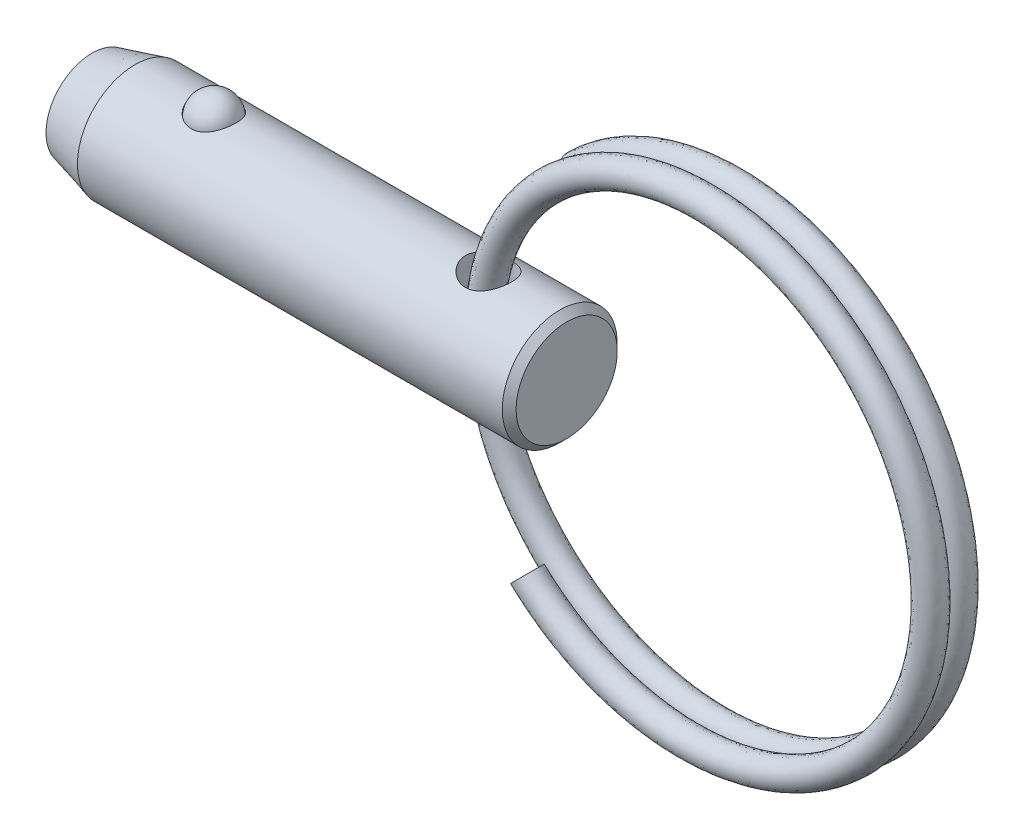
SolidWorks part; units mm, degrees
material "Plain Carbon Steel"
ref_plane "Front" through (0, 0, 0) normal (0, 0, 1) x (1, 0, 0)
ref_plane "Top" through (0, 0, 0) normal (0, 1, 0) x (1, 0, 0)
ref_plane "Right" through (0, 0, 0) normal (1, 0, 0) x (0, 0, -1)
sketch "Sketch1" plane through (0, 0, 0) normal (0, 0, 1) x (1, 0, 0)
  line L0 (13.1064, 2.794) -> (12.7254, 3.175)
  line L1 (12.7254, 3.175) -> (13.1064, 3.175) construction
  line L4 (13.1064, 2.794) -> (13.1064, 0)
  line L5 (13.1064, 3.175) -> (13.1064, 2.794) construction
  line L16 (12.7254, 3.175) -> (-10.7365, 3.175)
  line L17 (-13.1064, 3.175) -> (-13.1064, 2.54) construction
  line L19 (-10.7365, 3.175) -> (-13.1064, 3.175) construction
  line L22 (-13.1064, -3.175) -> (-10.7365, -3.175) construction
  line L23 (-6.3719, 2.8575) -> (-6.3719, -2.8575) construction
  line L24 (-13.1064, 0) -> (13.1064, 0)
  line L27 (13.1064, 0) -> (15.9004, 0) construction
  line L29 (-13.1064, 0) -> (-13.1064, -2.54) construction
  line L36 (7.5184, 0) -> (7.5184, 3.175) construction
  line L37 (-13.1064, 2.54) -> (-13.1064, 0)
  line L38 (-10.7365, -3.175) -> (13.1064, -3.175) construction
  line L39 (-13.1064, -2.54) -> (-13.1064, -3.175) construction
  line L40 (-10.7365, 3.175) -> (-13.1064, 2.54)
  line L42 (-10.7365, -3.175) -> (-13.1064, -2.54) construction
  line L43 (-10.7365, 3.175) -> (-10.7365, -3.175) construction
  circle A2 centre (-6.3719, 2.8575) radius 1.2319 construction
  point P35 (-5.1816, 3.175)
  dimension "A1" = 15
revolve "Revolve1" add sketch "Sketch1" angle 360 about L27
sketch "Sketch2" plane through (0, 0, 0) normal (0, 0, 1) x (1, 0, 0)
  line L0 (-5.1146, 2.8575) -> (-7.6292, 2.8575)
  line L1 (-6.3719, 4.0894) -> (-6.3719, 4.1148) construction
  line L2 (-5.1146, 2.8575) -> (-2.6, 2.8575) construction
  circle A0 centre (-6.3719, 2.8575) radius 1.2319 construction
  circle A1 centre (-6.3719, 2.8575) radius 1.2319 construction
  arc A2 (-7.6292, 2.8575) -> (-5.1146, 2.8575) centre (-6.3719, 2.8575) cw
  dimension "D1" = 0.0254
revolve "Cut-Revolve1" cut sketch "Sketch2" angle 360 about L2
sketch "Sketch3" plane through (0, 0, 0) normal (0, 0, 1) x (1, 0, 0)
  line L0 (-5.14, 2.8575) -> (-7.6038, 2.8575)
  line L1 (-5.14, 2.8575) -> (-2.6762, 2.8575) construction
  circle A0 centre (-6.3719, 2.8575) radius 1.2319 construction
  arc A1 (-5.14, 2.8575) -> (-7.6038, 2.8575) centre (-6.3719, 2.8575) ccw
revolve "Revolve2" add sketch "Sketch3" angle 360 about L1
sketch "Sketch4" plane through (0, 0, 0) normal (0, 0, 1) x (1, 0, 0)
  line L1 (8.7884, -3.175) -> (10.0584, -3.175)
  line L2 (8.7884, -3.175) -> (8.7884, 3.175)
  line L3 (8.7884, 3.175) -> (10.0584, 3.175)
  line L4 (10.0584, -3.175) -> (10.0584, 3.175)
  line L5 (8.7884, -3.175) -> (8.7884, -4.445) construction
  line L6 (10.0584, 3.175) -> (13.1064, 3.175) construction
  line L8 (7.5184, -3.175) -> (7.5184, 3.175) construction
  line L9 (7.5184, 0) -> (8.7884, 0) construction
  line L11 (8.7884, 0) -> (10.0584, 0) construction
  line L12 (12.7254, 3.175) -> (-10.7365, 3.175) construction
  line L14 (-10.7365, -3.175) -> (13.1064, -3.175) construction
  dimension "D1" = 2.54
revolve "Cut-Revolve2" cut sketch "Sketch4" angle 360 about L2
sketch "Sketch5" plane through (0, 0, 0) normal (0, 0, 1) x (1, 0, 0)
  line L0 (0, 0) -> (7.8114, 0) construction
  line L1 (7.8114, 0) -> (7.8114, 3.175) construction
  line L2 (12.7254, 3.175) -> (-10.7365, 3.175) construction
  line L3 (21.2734, 0) -> (34.7354, 0) construction
  line L4 (10.0584, 3.175) -> (9.7654, 3.175) construction
  line L5 (8.7884, 3.175) -> (10.0584, 3.175) construction
  line L6 (8.1912, 3.175) -> (8.1912, -3.175) construction
  line L7 (7.8114, 3.175) -> (7.5184, 3.175) construction
  line L8 (8.7884, -3.175) -> (10.0584, -3.175) construction
  line L9 (8.1912, -3.175) -> (10.0584, -3.175) construction
  line L10 (7.8114, 0) -> (21.2734, 0) construction
  line L12 (9.7654, 3.175) -> (8.1912, 3.175) construction
  line L13 (21.2734, 11.938) -> (21.2734, 13.462) construction
  circle A0 centre (21.2734, 0) radius 13.462
  circle A1 centre (21.2734, 0) radius 11.938 construction
  circle A2 centre (21.2734, 0) radius 12.7 construction
  point P26 (21.2734, 12.7)
curve "Helix/Spiral1" pitch 1.5494 height 1.3557 radius 13.462 left hand yes centre (21.2734, 0, 0) axis (0, 0, -1) start towards (1, 0, 0)
sketch "Sketch6" plane through (114.0038, 0, 0) normal (0, 1, 0) x (0, 0, -1)
  line L0 (0, 104.6684) -> (0, 105.4304) construction
  line L1 (0, 105.4304) -> (0, 106.1924) construction
  circle A0 centre (0, 105.4304) radius 0.762
  dimension "D1" = 1.524
sketch "Sketch7" plane through (0, 0, 0) normal (0, 0, 1) x (1, 0, 0)
  circle A0 centre (21.2734, 0) radius 13.462 construction
  circle A1 centre (21.2734, 0) radius 13.462
curve "Helix/Spiral2" pitch 1.5494 height 1.3557 radius 13.462 left hand yes centre (21.2734, 0, 0) axis (0, 0, 1) start towards (1, 0, 0)
sweep "Sweep1" add profiles "Sketch6" path "Helix/Spiral1"
sweep "Sweep2" add profiles "Sketch6<2>" path "Helix/Spiral2"
sketch "Sketch6<2>" plane through (114.0038, 0, 0) normal (0, 1, 0) x (0, 0, -1) same geometry as "Sketch6"
equation "\"D12@Sketch1\"=\"A@Sketch1\" * 0.80"
equation "\"D2@Sketch1\"=\"A@Sketch1\" * 0.9"
equation "\"D1@Sketch4\" = \"A@Sketch1\" / 2.5"
equation "\"Ring OD@Sketch5\" = \"R Ring Dia@Sketch5\" * 0.06"
equation "\"D4@Helix/Spiral1\"=\"Ring OD@Sketch5\" + 0.001"
equation "\"D1@Sketch6\"=\"Ring OD@Sketch5\""
equation "\"D4@Helix/Spiral2\" = \"D4@Helix/Spiral1\""
equation "\"D5@Helix/Spiral2\" = \"D5@Helix/Spiral1\""
